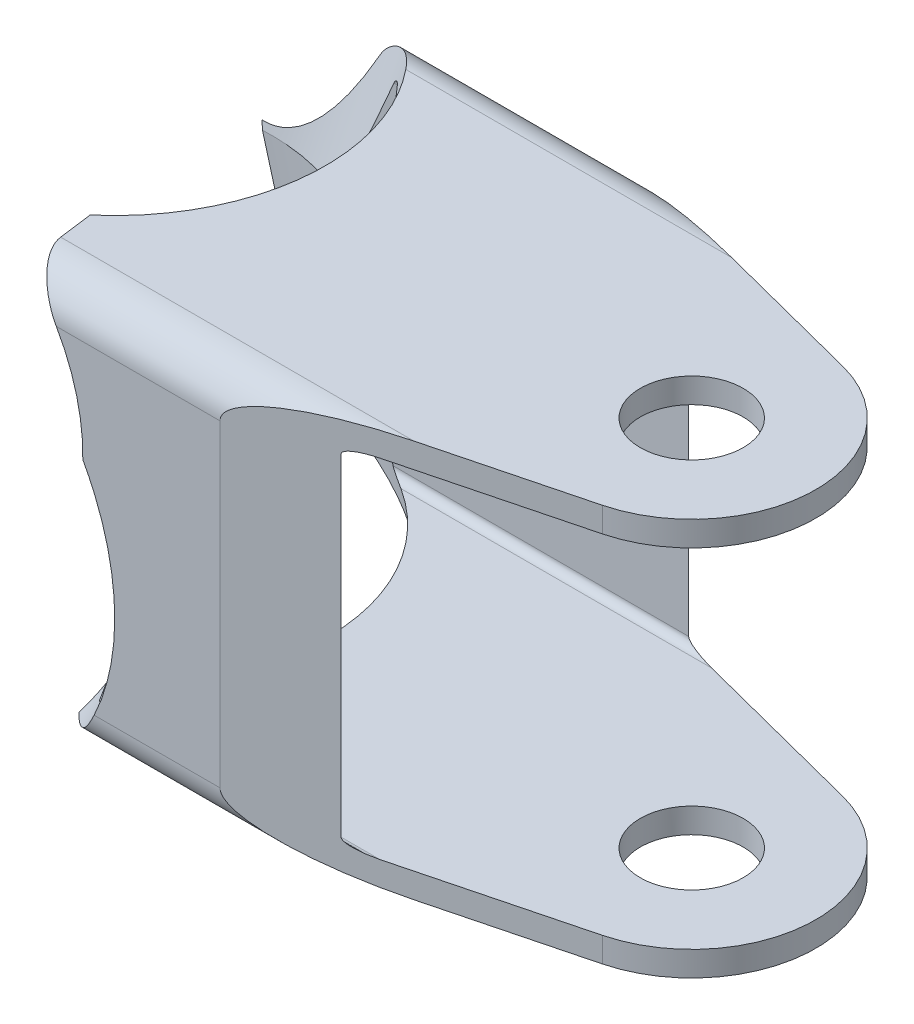
SolidWorks part; units mm, degrees
note: '?' marks a value the reader was unsure of.
material "AISI 4130 Steel, annealed at 865C"
ref_plane "Front Plane" through (0, 0, 0) normal (0, 0, 1) x (1, 0, 0)
ref_plane "Top Plane" through (0, 0, 0) normal (0, 1, 0) x (1, 0, 0)
ref_plane "Right Plane" through (0, 0, 0) normal (1, 0, 0) x (0, 0, -1)
sketch "Sketch1" plane through (0, 0, 0) normal (1, 0, 0) x (0, 0, -1)
  line L1 (-10.16, 12.7) -> (10.16, 12.7)
  line L2 (-12.7, 10.16) -> (-12.7, -10.16)
  line L3 (-10.16, -12.7) -> (10.16, -12.7)
  line L4 (12.7, 10.16) -> (12.7, -10.16)
  arc A0 (-10.16, 12.7) -> (-12.7, 10.16) centre (-10.16, 10.16) ccw
  arc A1 (-10.16, -12.7) -> (-12.7, -10.16) centre (-10.16, -10.16) cw
  arc A2 (10.16, 12.7) -> (12.7, 10.16) centre (10.16, 10.16) cw
  arc A3 (12.7, -10.16) -> (10.16, -12.7) centre (10.16, -10.16) cw
  point P4 (0, -12.7)
  point P7 (0, 0)
  point P15 (12.7, 0)
  dimension "D3" = 2.54
  dimension "D4" = 2.54
  dimension "D5" = 2.54
  dimension "D6" = 2.54
  dimension "D1" = 25.4
  dimension "D2" = 20.32
extrude "Boss-Extrude1" add sketch "Sketch1" along normal blind 25.4 and the other way blind 34.925
sketch "Sketch11" plane through (25.4, 0, 0) normal (1, 0, 0) x (0, 0, -1)
  line L0 (-10.16, -12.7) -> (10.16, -12.7) construction
  line L1 (-10.6045, 11.1125) -> (10.6045, 11.1125)
  line L2 (-11.1125, 10.6045) -> (-11.1125, -10.6045)
  line L3 (-10.6045, -11.1125) -> (10.6045, -11.1125)
  line L4 (11.1125, 10.6045) -> (11.1125, -10.6045)
  line L5 (10.16, 12.7) -> (-10.16, 12.7) construction
  line L6 (12.7, -10.16) -> (12.7, 10.16) construction
  line L7 (-12.7, 10.16) -> (-12.7, -10.16) construction
  arc A0 (10.6045, 11.1125) -> (11.1125, 10.6045) centre (10.6045, 10.6045) cw
  arc A1 (10.6045, -11.1125) -> (11.1125, -10.6045) centre (10.6045, -10.6045) ccw
  arc A2 (-11.1125, -10.6045) -> (-10.6045, -11.1125) centre (-10.6045, -10.6045) ccw
  arc A3 (-10.6045, 11.1125) -> (-11.1125, 10.6045) centre (-10.6045, 10.6045) ccw
  dimension "D1" = 1.5875
  dimension "D2" = 1.5875
  dimension "D3" = 1.5875
  dimension "D4" = 1.5875
  dimension "D5" = 0.508
extrude "Cut-Extrude4" cut sketch "Sketch11" against normal through all
sketch "Sketch12" plane through (0, 12.7, 0) normal (0, 1, 0) x (1, 0, 0)
  line L1 (0, 12.7) -> (50.8, 12.7)
  line L2 (50.8, 12.7) -> (50.8, -12.7)
  line L12 (50.8, -12.7) -> (0, -12.7)
  line L13 (19.4444, -7.6861) -> (0, -12.7)
  line L14 (19.4444, 7.6861) -> (0, 12.7)
  line L15 (-34.925, -12.7) -> (25.4, -12.7) construction
  line L16 (-34.925, 12.7) -> (25.4, 12.7) construction
  line L18 (25.4, 10.16) -> (25.4, -10.16) construction
  arc A1 (19.4444, -7.6861) -> (19.4444, 7.6861) centre (17.4625, 0) ccw
  point P8 (18.1688, 9.2165)
  dimension "D2" = 50.8
  dimension "D1" = 17.4625
extrude "Cut-Extrude5" cut sketch "Sketch12" against normal through all
sketch "Sketch14" plane through (0, 12.7, 0) normal (0, 1, 0) x (1, 0, 0)
  circle A0 centre (17.4625, 0) radius 3.2893
  arc A2 (19.4444, -7.6861) -> (19.4444, 7.6861) centre (17.4625, 0) ccw construction
  point P0 (17.4625, 0)
  point P6 (25.4, 0)
  dimension "D2" = 6.5786
  dimension "D1" = 7.9375
  dimension "D3" = 17.4625
extrude "Cut-Extrude6" cut sketch "Sketch14" against normal through all
ref_axis "Axis1" through (-38.1215, 60.4538, 0.5471) along (0.2581, -0.9661, -0.0075)?
ref_axis "Axis2" through (-23.0524, 2.8538, 0.2443) along (0.1865, 0.9626, -0.1964)?
ref_axis "Axis3" through (-102.6436, -17.7543, 0.1041) along (0.9661, 0.2581, 0)?
ref_axis "Axis4" through (-14.632, 5.1648, 75.9316) along (-0.1086, -0.0213, -0.9939)?
ref_axis "Axis5" through (-21.9028, 1.5156, 4.2211) along (0.2163, -0.431, 0.876)?
ref_point "Point1"
ref_point "Point2"
ref_point "Point3"
ref_point "Point4"
ref_point "Point5"
ref_plane "Plane1" through (-25.3657, 12.7, 0.1754) normal (0.2581, -0.9661, -0.0075) x (-0.9661, -0.2581, -0.002)
ref_plane "Plane2" through (-21.1452, 12.7, -1.7643) normal (-0.1865, -0.9626, 0.1964) x (-0.9825, 0.1827, -0.0373)
ref_plane "Plane3" through (-34.925, 0.3344, 0.1041) normal (0.9661, 0.2581, 0) x (0, 0, -1)
ref_plane "Plane4" through (-21.5426, 3.811, 12.7) normal (-0.1086, -0.0213, -0.9939) x (-0.9941, 0.0023, 0.1086)
ref_plane "Plane5" through (-19.8094, -2.6562, 12.7) normal (-0.2163, 0.431, -0.876) x (-0.9763, -0.0955, 0.1941)
sketch "Sketch15" plane through (-25.3657, 12.7, 0.1754) normal (0.2581, -0.9661, -0.0075) x (-0.9661, -0.2581, -0.002)
  circle A0 centre (0, 0) radius 12.7
sketch "Sketch16" plane through (-21.1452, 12.7, -1.7643) normal (-0.1865, -0.9626, 0.1964) x (-0.9825, 0.1827, -0.0373)
  circle A0 centre (0, 0) radius 12.7
sketch "Sketch17" plane through (-34.925, 0.3344, 0.1041) normal (0.9661, 0.2581, 0) x (0, 0, -1)
  circle A0 centre (0, 0) radius 12.7
sketch "Sketch18" plane through (-21.5426, 3.811, 12.7) normal (-0.1086, -0.0213, -0.9939) x (-0.9941, 0.0023, 0.1086)
  circle A0 centre (0, 0) radius 12.7
sketch "Sketch19" plane through (-19.8094, -2.6562, 12.7) normal (-0.2163, 0.431, -0.876) x (-0.9763, -0.0955, 0.1941)
  circle A0 centre (0, 0) radius 12.7
extrude "Cut-Extrude7" cut sketch "Sketch15" against normal blind 12.7 and the other way blind 76.2
extrude "Cut-Extrude8" cut sketch "Sketch16" against normal blind 25.4 and the other way blind 10.668
extrude "Cut-Extrude9" cut sketch "Sketch17" against normal blind 25.4 and the other way blind 13.462
extrude "Cut-Extrude10" cut sketch "Sketch18" against normal blind 25.4 and the other way blind 11.43
extrude "Cut-Extrude11" cut sketch "Sketch19" against normal blind 25.4 and the other way blind 10.668
ref_plane "Plane6" through (-20.5099, -5.4785, 0) normal (-0.9661, -0.2581, 0) x (0.2581, -0.9661, -0.0075)
sketch "Sketch20" plane through (-20.5099, -5.4785, 0) normal (-0.9661, -0.2581, 0) x (0.2581, -0.9661, -0.0075)
  line L1 (-25.07, 16.3096) -> (21.849, 16.3096)
  line L2 (-25.07, 16.3096) -> (-25.07, -19.8226)
  line L3 (-25.07, -19.8226) -> (21.849, -19.8226)
  line L4 (21.849, 16.3096) -> (21.849, -19.8226)
extrude "Cut-Extrude12" cut sketch "Sketch20" along normal through all
